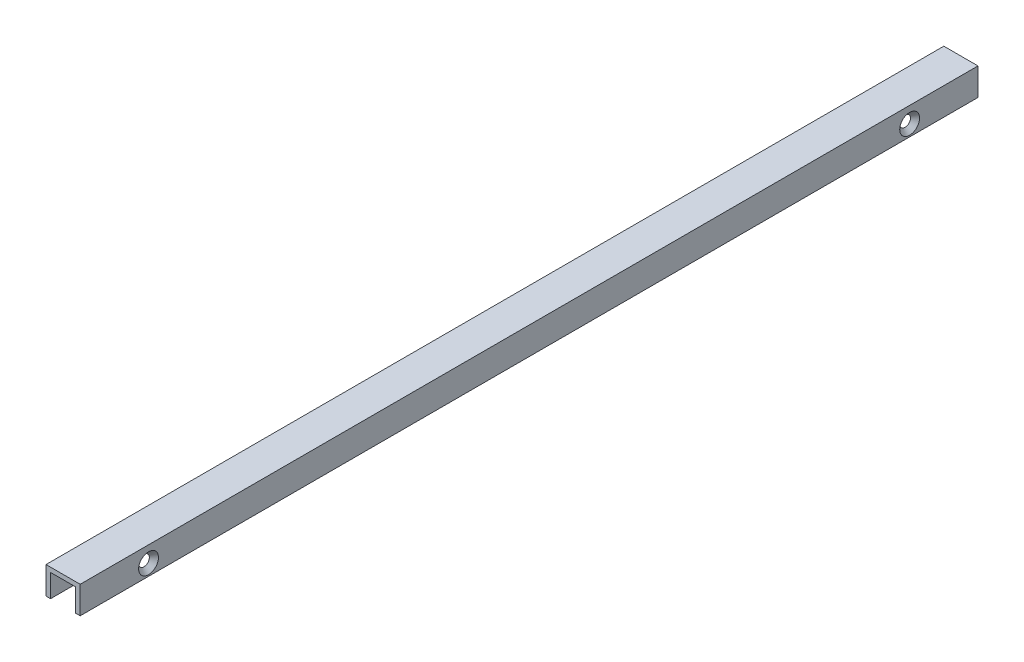
SolidWorks part; units mm, degrees
note: The reader was unsure of these and kept them because the rebuilt part matched: thickness of "Базовая кромка2", "Листовой металл2", "Листовой металл3".
material "1060 Сплав"
ref_plane "Front" through (0, 0, 0) normal (0, 0, 1) x (1, 0, 0)
ref_plane "Top" through (0, 0, 0) normal (0, 1, 0) x (1, 0, 0)
ref_plane "Right" through (0, 0, 0) normal (1, 0, 0) x (0, 0, -1)
sketch "Эскиз6" plane through (0, 0, 0) normal (0, 0, 1) x (1, 0, 0)
  line L0 (0, 0) -> (-2, 0)
  line L1 (-2, 0) -> (-2, 12)
  line L2 (-2, 12) -> (13, 12)
  line L3 (13, 12) -> (13, 0)
  line L4 (0, 10) -> (11, 10)
  line L5 (13, 0) -> (11, 0)
  line L6 (11, 0) -> (11, 10)
  line L7 (0, 10) -> (0, 0)
  dimension "D1" = 12
  dimension "D2" = 2
  dimension "D3" = 15
  dimension "D4" = 2
  dimension "D5" = 2
base flange "Базовая кромка2" sketch "Эскиз6" thickness 394 reverse thickness direction no parameters "D1"=0
sketch "Эскиз7" plane through (13, 0, 0) normal (1, 0, 0) x (0, 0, -1)
  line L0 (0, 0) -> (0, 12) construction
  line L1 (394, 0) -> (0, 0) construction
  line L2 (394, 0) -> (394, 12) construction
  circle A0 centre (30, 5) radius 2.3
  circle A1 centre (364, 5) radius 2.3
  dimension "D1" = 4.6
  dimension "D2" = 30
  dimension "D3" = 5
  dimension "D4" = 4.6
  dimension "D5" = 30
  dimension "D6" = 5
extrude "Вырез-Вытянуть1" cut sketch "Эскиз7" against normal blind 2 normal cut yes
chamfer "Фаска1" distance 2.05 angle 45 2 edges at (13, 5, -366.3) (13, 5, -32.3)
sketch "Сгиб-Линии3" [suppressed] plane through (0, 0, 0) normal (0, 1, 0) x (1, 0, 0)
sketch "Граничная рамка3" [suppressed] plane through (0, 0, 0) normal (0, 1, 0) x (1, 0, 0)
sheet metal parameters "Листовой металл2" thickness 394 parameters "D1"=0
flat pattern "Развертка2" [suppressed]
sketch "Сгиб-Линии4" plane through (0, 0, 0) normal (0, 1, 0) x (1, 0, 0)
sketch3d "Граничная рамка4" [suppressed]
  line L0 (-2, 0, 0) -> (13, 0, 0) construction
  line L1 (-2, 10, 0) -> (13, 10, 0) construction
  line L2 (-2, 0, 0) -> (-2, 10, 0) construction
  line L3 (13, 0, 0) -> (13, 10, 0) construction
sheet metal parameters "Листовой металл3" thickness 394 parameters "D1"=0
flat pattern "Развертка2"
sketch "Сгиб-Линии4" plane through (0, 0, 0) normal (0, 1, 0) x (1, 0, 0)
sketch3d "Граничная рамка4" [suppressed]
  line L0 (-2, 0, 0) -> (13, 0, 0) construction
  line L1 (-2, 12, 0) -> (13, 12, 0) construction
  line L2 (-2, 0, 0) -> (-2, 12, 0) construction
  line L3 (13, 0, 0) -> (13, 12, 0) construction
